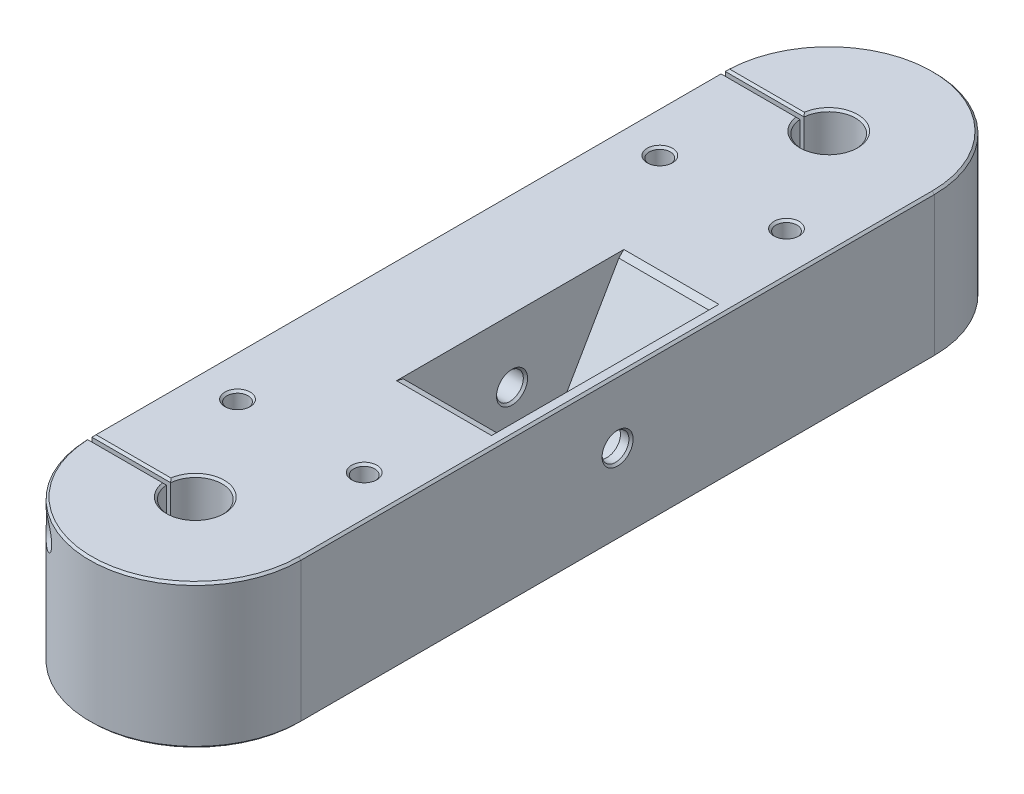
SolidWorks part; units mm, degrees
note: The reader was unsure of these and kept them because the rebuilt part matched: shared geometry of "Sketch2<6>", "Sketch2<7>", "Sketch4<2>".
material "Nylon 101"
ref_plane "Front" through (0, 0, 0) normal (0, 0, 1) x (1, 0, 0)
ref_plane "Top" through (0, 0, 0) normal (0, 1, 0) x (1, 0, 0)
ref_plane "Right" through (0, 0, 0) normal (1, 0, 0) x (0, 0, -1)
sketch "Sketch1" plane through (0, 0, 0) normal (0, 1, 0) x (1, 0, 0)
  line L0 (-25, -75) -> (6.35, -75) construction
  line L1 (-15, 50) -> (15, 50) construction
  line L2 (0, -75) -> (0, 75) construction
  line L3 (-25, -75) -> (-25, 75)
  line L4 (25, -75) -> (25, 75)
  line L5 (25, 0) -> (0, 0) construction
  line L10 (-15, 50) -> (-15, -50) construction
  line L11 (-15, -50) -> (15, -50) construction
  line L12 (15, 50) -> (15, -50) construction
  line L13 (-25, -75.5) -> (6.3303, -75.5)
  line L14 (-25, -74.5) -> (6.3303, -74.5)
  line L15 (-25, 75.5) -> (6.3303, 75.5)
  line L16 (-25, 74.5) -> (6.3303, 74.5)
  line L17 (-25, -74.5) -> (25, -74.5) construction
  line L18 (-25, -75) -> (25, -75) construction
  line L19 (24.995, -75.5) -> (25, -75.5)
  line L20 (-25, -75.5) -> (25, -75.5) construction
  line L21 (24.995, 75.5) -> (25, 75.5)
  circle A0 centre (0, 75) radius 6.35
  circle A1 centre (0, -75) radius 6.35
  arc A2 (-25, -75) -> (25, -75) centre (0, -75) ccw
  arc A3 (25, 75) -> (-25, 75) centre (0, 75) ccw
  circle A6 centre (-15, 50) radius 2.5
  circle A7 centre (-15, -50) radius 2.5
  circle A8 centre (15, -50) radius 2.5
  circle A9 centre (15, 50) radius 2.5
  point P8 (0, 0)
  point P14 (24.995, 102.1824)
  point P24 (0, -50)
  dimension "D2" = 12.7
  dimension "D5" = 25
  dimension "D1" = 5
  dimension "D3" = 150
  dimension "D4" = 25
  dimension "D6" = 25
  dimension "D9" = 30
  dimension "D10" = 0.5
  dimension "D11" = 0.5
extrude "Boss-Extrude1" add sketch "Sketch1" along normal blind 10 and the other way blind 24.004 contours A1 L14 L4 L16 A0 L3 A9 A8 A7 A6
sketch "Sketch2" plane through (0, 0, 0) normal (0, 0, 1) x (1, 0, 0)
  line L0 (0, 0) -> (-25, 0) construction
  line L1 (-6.35, 0) -> (-6.35, 10) construction
  line L3 (-6.35, 5) -> (-24.995, 5) construction
  line L5 (25, 10) -> (-24.995, 10) construction
  line L6 (-24.995, -24.004) -> (-24.995, 10) construction
  circle A0 centre (-15.6725, 5) radius 3.5
  circle A1 centre (-15.6725, 5) radius 1.75
  circle A2 centre (-15.6725, 5) radius 1.25
  point P7 (0, 0)
  point P8 (-6.35, 10)
  point P17 (-14.2504, 5)
  point P18 (-24.995, 5)
  dimension "D2" = 7
  dimension "D3" = 3.5
  dimension "D4" = 2.5
  dimension "D1" = 6.35
extrude "Cut-Extrude1" cut sketch "Sketch2" against normal through all from offset 80 contours A0 A1 | A1 A2 | A2 offset against normal yes
extrude "Cut-Extrude2" cut sketch "Sketch2<6>" against normal through all from surface at -75.5 contours A2 | A1 A2 starting at face at (-15.6626, -7.002, -75.5)
sketch "Sketch2<6>" plane through (0, 0, 0) normal (0, 0, 1) x (1, 0, 0) same geometry as "Sketch2"
extrude "Cut-Extrude3" cut sketch "Sketch2<7>" along normal blind 15 from surface at -74.5 contours A2 starting at face at (-15.6651, -7.002, -74.5)
sketch "Sketch2<7>" plane through (0, 0, 0) normal (0, 0, 1) x (1, 0, 0) same geometry as "Sketch2"
sketch "Sketch3" plane through (0, 0, 0) normal (0, 0, 1) x (1, 0, 0)
  line L1 (-27.3605, 12.3986) -> (30.5984, 12.3986)
  line L2 (-27.3605, 12.3986) -> (-27.3605, -26.5645)
  line L3 (-27.3605, -26.5645) -> (30.5984, -26.5645)
  line L4 (30.5984, 12.3986) -> (30.5984, -26.5645)
extrude "Cut-Extrude4" cut sketch "Sketch3" along normal through all
mirror "Mirror1" about plane through (0, 0, 0) normal (0, 0, 1) of bodies 120
sketch "Sketch4" plane through (-25, 0, 0) normal (-1, 0, 0) x (0, 0, 1)
  line L0 (-25.9808, 10) -> (25.9808, 10)
  line L1 (74.5, 10) -> (-74.5, 10) construction
  line L2 (25.9808, 10) -> (12.9904, -12.5)
  line L3 (-12.9904, -12.5) -> (-25.9808, 10)
  line L4 (0, 0) -> (0, -5) construction
  circle A0 centre (0, -5) radius 3.175
  arc A1 (-12.9904, -12.5) -> (12.9904, -12.5) centre (0, -5) ccw
  dimension "D1" = 6.35
  dimension "D2" = 5
  dimension "D3" = 15
  dimension "D4" = 60
extrude "Cut-Extrude5" cut sketch "Sketch4" against normal offset from surface (22.5 mm away) 2.5 from offset 25 up to face at (25, -7.002, 0) offset against normal yes
extrude "Cut-Extrude6" cut sketch "Sketch4<2>" against normal through all
sketch "Sketch4<2>" plane through (-25, 0, 0) normal (-1, 0, 0) x (0, 0, 1) same geometry as "Sketch4"
chamfer "Chamfer1" distance 0.5 angle 45 40 edges at (-15, 10, -47.5) (-15.6651, 10, -74.5) (6.35, 10, -75) (-15.6626, 10, -75.5) (0.25, 10, -99.9987) (25, 10, 0) (0.25, -24.004, 99.9987) (0.25, 10, 99.9987) (-15.6626, -24.004, 75.5) (-15.6626, 10, 75.5) (6.35, -24.004, 75) (6.35, 10, 75) (-15.6651, -24.004, 74.5) (-15.6651, 10, 74.5) (-25, 10, 0) (-14.4225, 5, -74.5) (-14.4225, 5, -59.5) (-13.9225, 5, -80) (-13.9225, 5, -75.5) (-13.9225, 5, 80) (-13.9225, 5, 75.5) (0.25, -24.004, -99.9987) (-15.6626, -24.004, -75.5) (6.35, -24.004, -75) (-15.6651, -24.004, -74.5) (-25, -24.004, 0) (25, -24.004, 0) (-15, -24.004, -47.5) (15, -24.004, 47.5) (15, 10, 47.5) (-15, -24.004, 47.5) (-15, 10, 47.5) (15, 10, -47.5) (15, -24.004, -47.5) (-14.4225, 5, 74.5) (25, -5, 3.175) (0, -5, 3.175) (-25, -5, 3.175) (11.25, 10, 25.9808) (11.25, 10, -25.9808)
